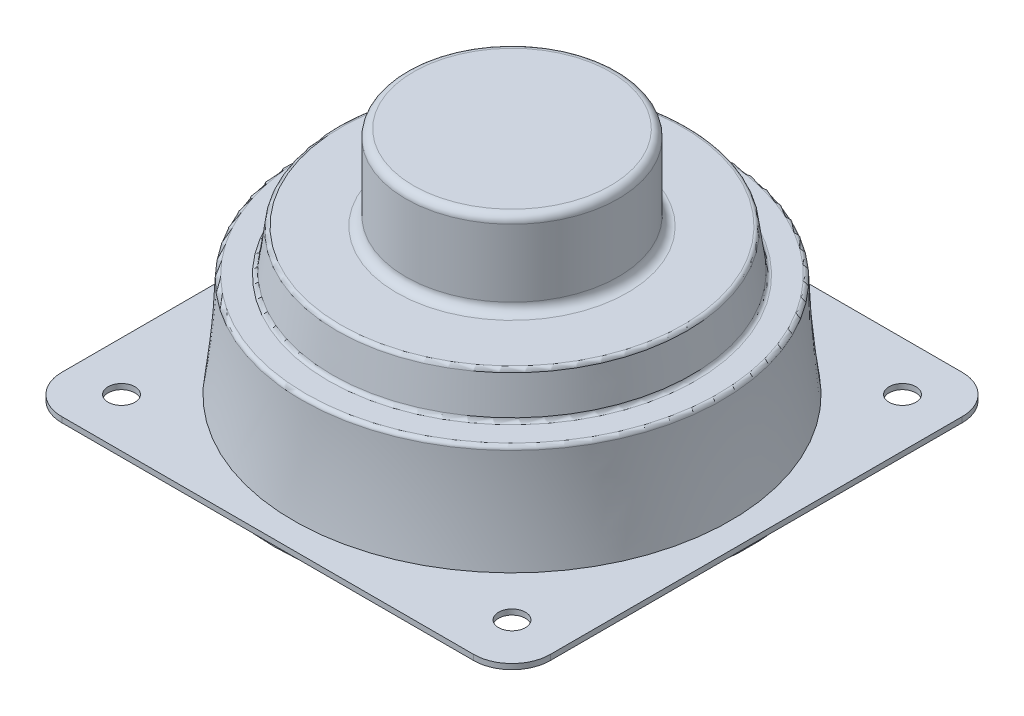
SolidWorks part; units mm, degrees
ref_plane "Front Plane" through (0, 0, 0) normal (0, 0, 1) x (1, 0, 0)
ref_plane "Top Plane" through (0, 0, 0) normal (0, 1, 0) x (1, 0, 0)
ref_plane "Right Plane" through (0, 0, 0) normal (1, 0, 0) x (0, 0, -1)
sketch "Sketch1" plane through (0, 0, 0) normal (0, 1, 0) x (1, 0, 0)
  line L1 (26.85, -31.85) -> (-26.85, -31.85)
  line L2 (31.85, -26.85) -> (31.85, 26.85)
  line L3 (26.85, 31.85) -> (-26.85, 31.85)
  line L4 (-31.85, -26.85) -> (-31.85, 26.85)
  line L5 (31.85, -31.85) -> (-31.85, 31.85) construction
  line L6 (31.85, 31.85) -> (-31.85, -31.85) construction
  arc A0 (-26.85, -31.85) -> (-31.85, -26.85) centre (-26.85, -26.85) cw
  arc A1 (26.85, -31.85) -> (31.85, -26.85) centre (26.85, -26.85) ccw
  arc A2 (31.85, 26.85) -> (26.85, 31.85) centre (26.85, 26.85) ccw
  arc A3 (-26.85, 31.85) -> (-31.85, 26.85) centre (-26.85, 26.85) ccw
  circle A4 centre (-25.4558, 25.4558) radius 1.75
  circle A5 centre (25.4558, -25.4558) radius 1.75
  circle A6 centre (25.4558, 25.4558) radius 1.75
  circle A7 centre (-25.4558, -25.4558) radius 1.75
  point P0 (0, 0)
  dimension "D2" = 5
  dimension "D7" = 3.5
  dimension "D1" = 63.7
  dimension "D3" = 36
  dimension "D4" = 36
  dimension "D5" = 36
  dimension "D6" = 36
extrude "Boss-Extrude1" add sketch "Sketch1" along normal blind 0.7
sketch "Sketch2" plane through (0, 0, 0) normal (0, -1, 0) x (1, 0, 0)
  circle A0 centre (0, 0) radius 31
  dimension "D1" = 62
extrude "Boss-Extrude2" add sketch "Sketch2" along normal blind 1
sketch "Sketch3" plane through (0, -1, 0) normal (0, -1, 0) x (1, 0, 0)
  circle A0 centre (0, 0) radius 25.2
  dimension "D1" = 50.4
extrude "Boss-Extrude3" add sketch "Sketch3" along normal blind 2
sketch "Sketch4" plane through (0, 0.7, 0) normal (0, 1, 0) x (1, 0, 0)
  circle A0 centre (0, 0) radius 28.5
  dimension "D1" = 57
ref_plane "Plane1" through (0, 14.2, 0) normal (0, 1, 0) x (1, 0, 0)
sketch "Sketch5" plane through (0, 14.2, 0) normal (0, 1, 0) x (1, 0, 0)
  circle A0 centre (0, 0) radius 27.35
  dimension "D1" = 54.7
loft "Loft1" add profiles "Sketch4", "Sketch5" connector at (-9.7719, 0.7, 26.7724) connector at (-3.1037, 14.2, 27.1733)
sketch "Sketch6" plane through (0, 14.2, 0) normal (0, 1, 0) x (1, 0, 0)
  circle A0 centre (0, 0) radius 23.5
  dimension "D1" = 47
ref_plane "Plane2" through (0, 19.7, 0) normal (0, 1, 0) x (1, 0, 0)
sketch "Sketch7" plane through (0, 19.7, 0) normal (0, 1, 0) x (1, 0, 0)
  circle A0 centre (0, 0) radius 22.75
  dimension "D1" = 45.5
loft "Loft2" add profiles "Sketch6", "Sketch7" connector at (-5.0975, 14.2, 22.9405) connector at (-6.539, 19.7, 21.79)
sketch "Sketch8" plane through (0, 19.7, 0) normal (0, 1, 0) x (1, 0, 0)
  circle A0 centre (0, 0) radius 13.85
  dimension "D1" = 27.7
extrude "Boss-Extrude4" add sketch "Sketch8" along normal blind 11
fillet "Fillet1" radius 1 1 edges at (0, 30.7, 13.85)
fillet "Fillet2" radius 1.2 1 edges at (0, 19.7, 13.85)
fillet "Fillet3" radius 0.5 3 edges at (0, 14.2, 27.35) (0, 14.2, 23.5) (0, 19.7, 22.75)
sketch "Sketch11" plane through (0, 0.7, 0) normal (0, 1, 0) x (1, 0, 0)
  circle A0 centre (-25.4558, 25.4558) radius 1.75
  circle A1 centre (25.4558, 25.4558) radius 1.75
  circle A2 centre (25.4558, -25.4558) radius 1.8367
  circle A3 centre (-25.4558, -25.4558) radius 1.75
  circle A4 centre (-25.4558, -25.4558) radius 4.25
  circle A5 centre (25.4558, -25.4558) radius 4.25
  circle A6 centre (25.4558, 25.4558) radius 4.25
  circle A7 centre (-25.4558, 25.4558) radius 4.25
  dimension "D1" = 8.5
